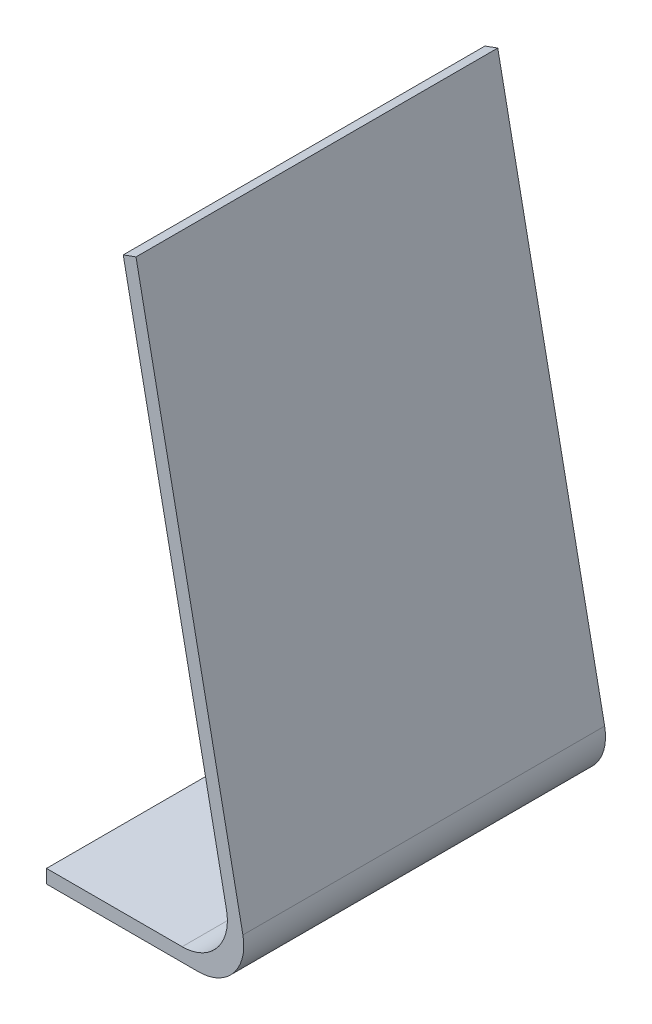
SolidWorks part; units mm, degrees
ref_plane "Front Plane" through (0, 0, 0) normal (0, 0, 1) x (1, 0, 0)
ref_plane "Top Plane" through (0, 0, 0) normal (0, 1, 0) x (1, 0, 0)
ref_plane "Right Plane" through (0, 0, 0) normal (1, 0, 0) x (0, 0, -1)
sketch "Sketch1" plane through (0, 0, 0) normal (0, 0, 1) x (1, 0, 0)
  line L0 (-50.53, 0) -> (-50.53, 3)
  line L1 (-50.53, 3) -> (-20.53, 3)
  line L2 (-50.53, 0) -> (-16.9035, 0)
  line L3 (-7.0982, 11.9638) -> (-30.7379, 130)
  line L4 (-30.7379, 130) -> (-33.5595, 128.9811)
  line L5 (-33.5595, 128.9811) -> (-10.7247, 14.9638)
  arc A0 (-10.7247, 14.9638) -> (-20.53, 3) centre (-20.53, 13) cw
  arc A1 (-16.9035, 0) -> (-7.0982, 11.9638) centre (-16.9035, 10) ccw
  dimension "D1" = 10
  dimension "D2" = 3
  dimension "D3" = 30
  dimension "D4" = 130
extrude "Boss-Extrude1" add sketch "Sketch1" along normal mid plane 80
